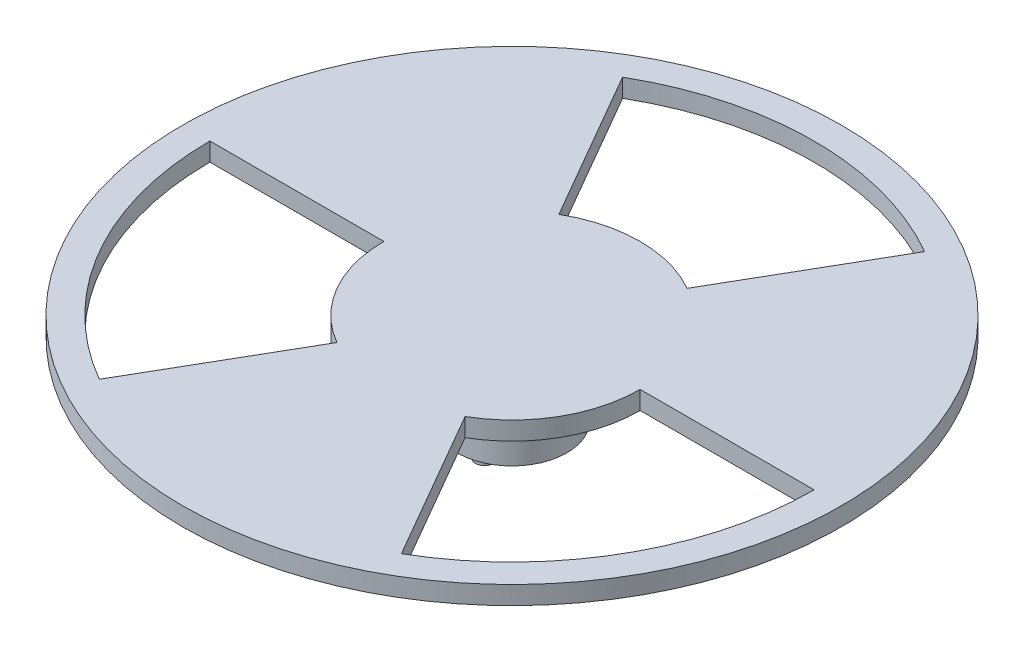
SolidWorks part; units mm, degrees
note: The reader was unsure of these and kept them because the rebuilt part matched: shared geometry of "Sketch4<3>".
ref_plane "Front Plane" through (0, 0, 0) normal (0, 0, 1) x (1, 0, 0)
ref_plane "Top Plane" through (0, 0, 0) normal (0, 1, 0) x (1, 0, 0)
ref_plane "Right Plane" through (0, 0, 0) normal (1, 0, 0) x (0, 0, -1)
sketch "Sketch1" plane through (0, 0, 0) normal (0, 1, 0) x (1, 0, 0)
  circle A0 centre (0, 0) radius 18
  dimension "D1" = 36
extrude "Boss-Extrude1" add sketch "Sketch1" along normal blind 1
sketch "Sketch4" plane through (0, 1, 0) normal (0, 1, 0) x (1, 0, 0)
  line L0 (-3.5, 6.0622) -> (-8.25, 14.2894)
  line L1 (3.5, 6.0622) -> (8.25, 14.2894)
  line L2 (0, 0) -> (0, 50000) construction
  line L3 (3.5, 6.0622) -> (0, 0) construction
  line L4 (0, 0) -> (-3.5, 6.0622) construction
  line L5 (7, 0) -> (16.5, 0)
  line L6 (3.5, -6.0622) -> (8.25, -14.2894)
  line L7 (-3.5, -6.0622) -> (-8.25, -14.2894)
  line L8 (-7, 0) -> (-16.5, 0)
  line L9 (0, 0) -> (43301.2702, 25000) construction
  arc A0 (-8.25, 14.2894) -> (8.25, 14.2894) centre (0, 0) cw
  circle A1 centre (0, 0) radius 18 construction
  arc A2 (-3.5, 6.0622) -> (3.5, 6.0622) centre (0, 0) cw
  arc A3 (16.5, 0) -> (8.25, -14.2894) centre (0, 0) cw
  arc A4 (7, 0) -> (3.5, -6.0622) centre (0, 0) cw
  arc A5 (-8.25, -14.2894) -> (-16.5, 0) centre (0, 0) cw
  arc A6 (-3.5, -6.0622) -> (-7, 0) centre (0, 0) cw
  circle A7 centre (1.299, 0.75) radius 0.5
  circle A8 centre (0, -1.5) radius 0.5
  circle A9 centre (-1.299, 0.75) radius 0.5
  dimension "D4" = 7
  dimension "D7" = 1
  dimension "D1" = 30
  dimension "D2" = 30
  dimension "D3" = 1.5
  dimension "D6" = 30
  dimension "D8" = 1.5
  dimension "D10" = 1.5
  dimension "D5" = 3
  dimension "D9" = 3
extrude "Cut-Extrude2" cut sketch "Sketch4" along a picked direction on the side against the normal up to surface (1 mm away) contours L0 A0 L1 A2
sketch "Sketch5" plane through (0, 0, 0) normal (0, -1, 0) x (1, 0, 0)
  circle A0 centre (0, 0) radius 3
  dimension "D1" = 6
extrude "Boss-Extrude2" add sketch "Sketch5" along normal blind 4 and the other way up to surface (1 mm away) other way up to face at (0, 1, -10.9629)
extrude "Boss-Extrude3" add sketch "Sketch4<3>" against normal blind 1 from surface at -5 contours A8 | A9 | A7 starting at face at (0, -4, -3)
sketch "Sketch4<3>" plane through (0, 1, 0) normal (0, 1, 0) x (1, 0, 0) same geometry as "Sketch4"
equation "\"D2@Sketch4\"=\"D1@Sketch4\""
equation "\"D6@Sketch4\"=\"D1@Sketch4\""
equation "\"D10@Sketch4\"=\"D8@Sketch4\""
